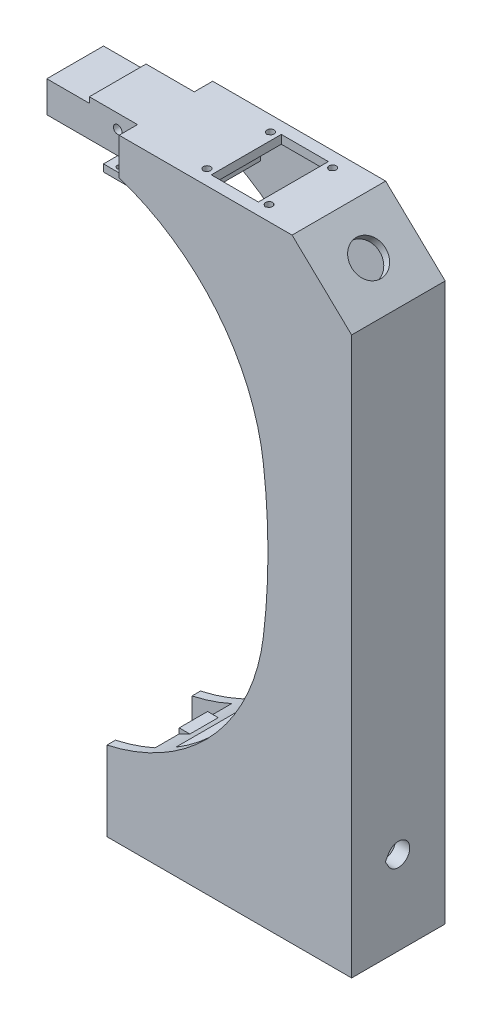
SolidWorks part; units mm, degrees
ref_plane "Спереди" through (0, 0, 0) normal (0, 0, 1) x (1, 0, 0)
ref_plane "Сверху" through (0, 0, 0) normal (0, 1, 0) x (1, 0, 0)
ref_plane "Справа" through (0, 0, 0) normal (1, 0, 0) x (0, 0, -1)
other "Configuration Table"
sketch "Эскиз1" plane through (0, 0, 0) normal (0, 0, 1) x (1, 0, 0)
  line L1 (4.2996, 175.4028) -> (4.2996, 188.4028)
  line L4 (86.2996, 0) -> (86.2996, 168.4028)
  line L7 (65.2996, 188.4028) -> (4.2996, 188.4028)
  line L11 (0, 0) -> (0, -28)
  line L12 (86.2996, 0) -> (86.2996, -28)
  line L13 (86.2996, -28) -> (0, -28)
  line L14 (65.2996, 188.4028) -> (86.2996, 168.4028)
  arc A0 (0, 0) -> (55.1731, 60.6624) centre (-15.2954, 69.3329) ccw
  arc A1 (55.1731, 113.6624) -> (4.2996, 175.4028) centre (-18.7693, 104.5645) ccw
  arc A2 (55.1731, 60.6624) -> (55.1731, 113.6624) centre (-160.2027, 87.1624) ccw
  dimension "D1" = 142
  dimension "D3" = 149
  dimension "D5" = 53
  dimension "D6" = 217
  dimension "D2" = 82
  dimension "D4" = 80
  dimension "D7" = 125.5129
  dimension "D8" = 126.3456
  dimension "D9" = 15.2954
  dimension "D10" = 69.3329
  dimension "D11" = 160.2027
  dimension "D12" = 87.1624
  dimension "D13" = 104.5645
  dimension "D14" = 18.7693
  dimension "D15" = 4.2996
  dimension "D16" = 175.4028
  dimension "D17" = 82
  dimension "D18" = 168.4028
  dimension "D19" = 61
  dimension "D20" = 28
  dimension "D21" = 86.2996
  dimension "D22" = 28
  dimension "D23" = 20
  dimension "D24" = 216.4028
extrude "Бобышка-Вытянуть6" add sketch "Эскиз1" along normal blind 33
sketch "Эскиз5" plane through (0, 0, 0) normal (0, 0, 1) x (1, 0, 0)
  line L3 (24.0996, 175.4028) -> (4.2996, 175.4028)
  line L4 (-18.7004, 169.1368) -> (-18.7004, -23.0234)
  line L8 (24.0996, 175.4028) -> (24.0996, 185.4028)
  line L9 (24.0996, 185.4028) -> (64.0996, 185.4028)
  line L10 (64.0996, 185.4028) -> (81.1789, 169.1368)
  line L11 (86.2996, 168.4028) -> (65.2996, 188.4028) construction
  line L12 (65.2996, 188.4028) -> (4.2996, 188.4028) construction
  line L13 (-18.7004, 169.1368) -> (4.2996, 169.1368)
  line L14 (4.2996, 169.1368) -> (4.2996, 175.4028)
  line L16 (81.1789, 8.4766) -> (14, 8.4766)
  line L19 (81.1789, 169.1368) -> (81.1789, 8.4766)
  line L20 (-18.7004, -23.0234) -> (14, -23.0234)
  line L21 (14, 8.4766) -> (14, -23.0234)
  dimension "D2" = 32.7004
  dimension "D3" = 31.5
  dimension "D4" = 3
  dimension "D5" = 3
  dimension "D6" = 40
  dimension "D7" = 23
  dimension "D8" = 67.1789
  dimension "D9" = 6.266
  dimension "D10" = 14
  dimension "D12" = 160.6602
extrude "Вырез-Вытянуть2" cut sketch "Эскиз5" along normal blind 27 from offset 3
sketch "Эскиз7" plane through (0, 0, 0) normal (0, 0, 1) x (1, 0, 0)
  line L1 (4.2996, 188.4028) -> (-27.7004, 188.4028)
  line L2 (4.2996, 188.4028) -> (4.2996, 175.4028)
  line L3 (4.2996, 175.4028) -> (-27.7004, 175.4028)
  line L4 (-27.7004, 188.4028) -> (-27.7004, 175.4028)
  dimension "D1" = 32
extrude "Бобышка-Вытянуть7" add sketch "Эскиз7" along normal blind 20 from offset 6.5
sketch "Эскиз11" plane through (0, 0, 0) normal (0, 0, 1) x (1, 0, 0)
  line L1 (10.2996, 175.4028) -> (-2.7004, 175.4028)
  line L2 (10.2996, 175.4028) -> (10.2996, 172.9028)
  line L3 (10.2996, 172.9028) -> (-2.7004, 172.9028)
  line L4 (-2.7004, 175.4028) -> (-2.7004, 172.9028)
  dimension "D1" = 6
  dimension "D2" = 2.5
  dimension "D3" = 13
  dimension "D4" = 7
extrude "Бобышка-Вытянуть15" add sketch "Эскиз11" along normal blind 30 from offset 1.5
sketch "Эскиз12" plane through (0, 0, 0) normal (0, 1, 0) x (1, 0, 0)
  line L1 (1.1427, -30.6547) -> (1.6427, -30.366)
  line L2 (1.1427, -30.6547) -> (0.6427, -30.366)
  line L4 (1.1427, -4.6547) -> (1.6427, -4.366)
  line L5 (1.1427, -4.6547) -> (0.6427, -4.366)
  arc A0 (1.6427, -4.366) -> (0.6427, -4.366) centre (1.1427, -3.5) ccw
  arc A1 (1.6427, -30.366) -> (0.6427, -30.366) centre (1.1427, -29.5) ccw
  dimension "D1" = 2
  dimension "D2" = 2
  dimension "D3" = 26
  dimension "D4" = 3.5
  dimension "D5" = 1.1427
  dimension "D6" = 1.1427
  dimension "D7" = 120
  dimension "D8" = 120
  dimension "D9" = 0.5
  dimension "D10" = 0.5
extrude "Вырез-Вытянуть3" cut sketch "Эскиз12" against normal blind 10 from offset 180
sketch "Эскиз13" plane through (0, 0, 0) normal (0, 0, 1) x (1, 0, 0)
  line L0 (4.2996, 188.4028) -> (-27.7004, 188.4028) construction
  line L1 (-27.7004, 188.4028) -> (-27.7004, 175.4028) construction
  circle A0 centre (-2.7004, 183.4028) radius 1.5
  dimension "D1" = 5
  dimension "D3" = 3
  dimension "D2" = 25
extrude "Вырез-Вытянуть4" cut sketch "Эскиз13" along normal blind 30
sketch "Эскиз14" plane through (0, 0, 0) normal (0, 0, 1) x (1, 0, 0)
  line L1 (-27.7004, 188.4028) -> (-12.7004, 188.4028)
  line L2 (-27.7004, 188.4028) -> (-27.7004, 186.4028)
  line L3 (-27.7004, 186.4028) -> (-12.7004, 186.4028)
  line L4 (-12.7004, 188.4028) -> (-12.7004, 186.4028)
  dimension "D1" = 2
  dimension "D2" = 15
extrude "Вырез-Вытянуть5" cut sketch "Эскиз14" along normal blind 30
sketch "Эскиз15" plane through (0, 0, 0) normal (0, 0, 1) x (1, 0, 0)
  line L1 (81.2996, -3.5) -> (14, -3.5)
  line L2 (81.2996, -3.5) -> (81.2996, 6.5)
  line L3 (81.2996, 6.5) -> (14, 6.5)
  line L4 (14, -3.5) -> (14, 6.5)
  dimension "D1" = 67.2996
  dimension "D2" = 10
  dimension "D3" = 5
  dimension "D4" = 24.5
extrude "Бобышка-Вытянуть16" add sketch "Эскиз15" along normal blind 10 from offset 11.5
sketch "Эскиз17" plane through (0, 0, 0) normal (1, 0, 0) x (0, 0, -1)
  line L1 (-21.1188, 1.5) -> (-19.9641, 3.5)
  line L2 (-21.1188, 1.5) -> (-19.9641, -0.5)
  arc A0 (-19.9641, -0.5) -> (-19.9641, 3.5) centre (-16.5, 1.5) ccw
  point P1 (0, 0)
  point P7 (0, 0)
  dimension "D1" = 8
  dimension "D2" = 1.5
  dimension "D3" = 16.5
  dimension "D4" = 120
  dimension "D5" = 2
extrude "Вырез-Вытянуть7" cut sketch "Эскиз17" along normal blind 75 from offset 17
sketch "Эскиз18" plane through (0, 0, 0) normal (1, 0, 0) x (0, 0, -1)
  line L1 (-18.8094, 1.5) -> (-18.2321, 2.5)
  line L2 (-18.8094, 1.5) -> (-18.2321, 0.5)
  arc A0 (-18.2321, 0.5) -> (-18.2321, 2.5) centre (-16.5, 1.5) ccw
  dimension "D1" = 4
  dimension "D2" = 120
  dimension "D3" = 1
extrude "Вырез-Вытянуть9" cut sketch "Эскиз18" along normal blind 5 from offset 13
sketch "Эскиз19" plane through (125.1475, 131.4049, 0) normal (0.6897, 0.7241, 0) x (0, 0, -1)
sketch "Эскиз20" plane through (0, 188.4028, 0) normal (0, 1, 0) x (1, 0, 0)
  line L4 (32.65, -4.15) -> (32.65, -28.85)
  line L5 (32.65, -28.85) -> (49.25, -28.85)
  line L6 (32.65, -4.15) -> (49.25, -4.15)
  line L7 (49.25, -4.15) -> (49.25, -28.85)
  line L9 (30, -29.1434) -> (30.625, -28.7825)
  line L10 (30, -29.1434) -> (29.375, -28.7825)
  line L12 (30, -6.7434) -> (30.625, -6.3825)
  line L13 (30, -6.7434) -> (29.375, -6.3825)
  line L16 (51.9, -6.7434) -> (52.525, -6.3825)
  line L17 (51.9, -6.7434) -> (51.275, -6.3825)
  line L20 (51.9, -29.1434) -> (52.525, -28.7825)
  line L21 (51.9, -29.1434) -> (51.275, -28.7825)
  arc A0 (52.525, -6.3825) -> (51.275, -6.3825) centre (51.9, -5.3) ccw
  arc A1 (52.525, -28.7825) -> (51.275, -28.7825) centre (51.9, -27.7) ccw
  arc A2 (30.625, -6.3825) -> (29.375, -6.3825) centre (30, -5.3) ccw
  arc A3 (30.625, -28.7825) -> (29.375, -28.7825) centre (30, -27.7) ccw
  dimension "D1" = 21.9
  dimension "D13" = 2.5
  dimension "D14" = 2.5
  dimension "D15" = 2.5
  dimension "D16" = 2.5
  dimension "D2" = 22.4
  dimension "D3" = 16.6
  dimension "D4" = 24.7
  dimension "D5" = 30
  dimension "D6" = 21.9
  dimension "D7" = 22.4
  dimension "D8" = 31.3268
  dimension "D9" = 32.65
  dimension "D10" = 4.15
  dimension "D11" = 51.9
  dimension "D12" = 27.7
  dimension "D17" = 49.25
  dimension "D18" = 120
  dimension "D19" = 120
  dimension "D20" = 120
  dimension "D21" = 120
  dimension "D22" = 0.625
  dimension "D23" = 0.625
  dimension "D24" = 0.625
  dimension "D25" = 0.625
extrude "Вырез-Вытянуть10" cut sketch "Эскиз20" against normal blind 5
sketch "Эскиз21" plane through (125.1475, 131.4049, 0) normal (0.6897, 0.7241, 0) x (0, 0, -1)
  line L0 (0, 53.6471) -> (0, 82.6471) construction
  line L1 (0, 68.1471) -> (-33, 68.1471)
  line L2 (-33, 53.6471) -> (-33, 82.6471) construction
  line L3 (-16.5, 82.6471) -> (-16.5, 53.6471)
  line L4 (-33, 82.6471) -> (0, 82.6471) construction
  line L5 (-33, 53.6471) -> (0, 53.6471) construction
  circle A0 centre (-16.5, 68.1471) radius 6
  point P17 (-16.5, 68.1471)
  dimension "D1" = 12
extrude "Вырез-Вытянуть11" cut sketch "Эскиз21" against normal blind 5 contours A0
sketch "Эскиз22" plane through (0, 0, 0) normal (0, 0, 1) x (1, 0, 0)
  line L1 (81.2996, -25) -> (30.2996, -25)
  line L2 (81.2996, -25) -> (81.2996, 22)
  line L3 (81.2996, 22) -> (30.2996, 22)
  line L4 (30.2996, -25) -> (30.2996, 22)
  dimension "D1" = 51
  dimension "D2" = 47
  dimension "D3" = 3
  dimension "D4" = 5
extrude "Вырез-Вытянуть12" cut sketch "Эскиз22" along normal blind 27 from offset 3
